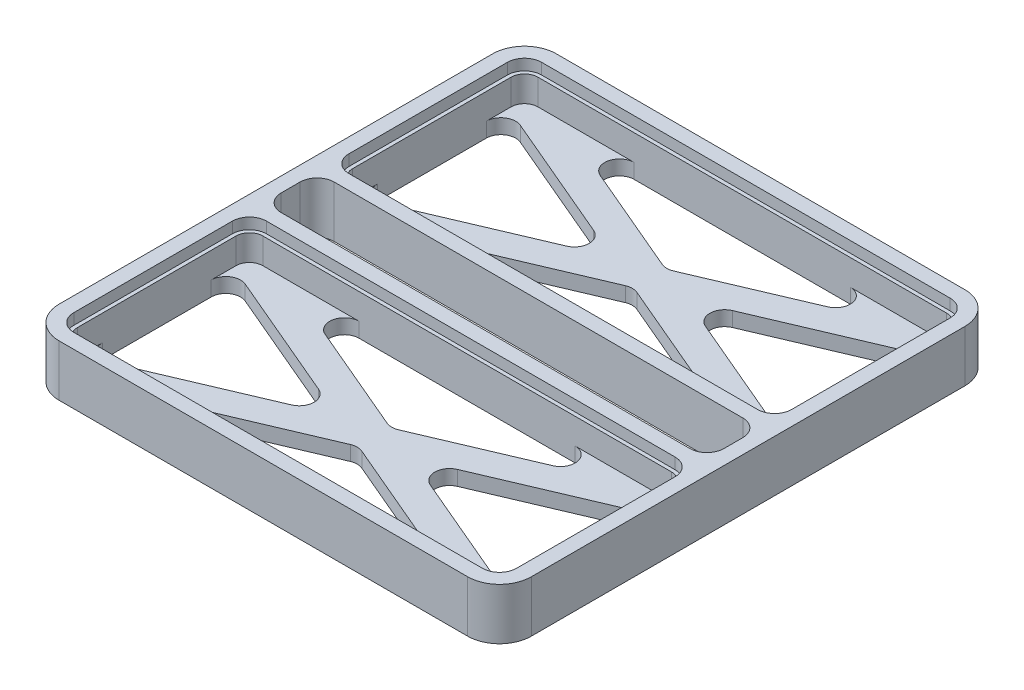
SolidWorks part; units mm, degrees
ref_plane "Спереди" through (0, 0, 0) normal (0, 0, 1) x (1, 0, 0)
ref_plane "Сверху" through (0, 0, 0) normal (0, 1, 0) x (1, 0, 0)
ref_plane "Справа" through (0, 0, 0) normal (1, 0, 0) x (0, 0, -1)
sketch "Эскиз1" plane through (0, 0, 0) normal (0, 1, 0) x (1, 0, 0)
  line L5 (14.6888, -12.6) -> (-14.6888, -12.6)
  line L6 (29.6, -7.4013) -> (29.6, 7.4013)
  line L7 (-32.1, -15.1) -> (32.1, -15.1)
  line L8 (-32.1, -15.1) -> (-32.1, 10.775)
  line L9 (-27.775, 15.1) -> (27.775, 15.1)
  line L10 (32.1, -15.1) -> (32.1, 10.775)
  line L11 (14.6888, 12.6) -> (-14.6888, 12.6)
  line L12 (-29.6, -7.4013) -> (-29.6, 7.4013)
  line L13 (-27.775, -52.5) -> (27.775, -52.5)
  line L14 (-0.7833, 2.5071) -> (-15.4722, 8.7598)
  line L15 (0.7833, 2.5071) -> (15.4722, 8.7598)
  line L16 (-9.4294, -1.8402) -> (-26.8167, -9.2415)
  line L17 (9.4294, -1.8402) -> (26.8167, -9.2415)
  line L18 (-0.7833, -2.5071) -> (-15.4722, -8.7598)
  line L19 (9.4294, 1.8402) -> (26.8167, 9.2415)
  line L20 (-0.7833, -34.8929) -> (-15.4722, -28.6402)
  line L21 (0.7833, -2.5071) -> (15.4722, -8.7598)
  line L22 (-9.4294, 1.8402) -> (-26.8167, 9.2415)
  line L23 (32.1, -48.175) -> (32.1, -22.3)
  line L24 (-9.4294, -39.2402) -> (-26.8167, -46.6415)
  line L25 (14.6888, -24.8) -> (-14.6888, -24.8)
  line L26 (0.7833, -39.9071) -> (15.4722, -46.1598)
  line L27 (-9.4294, -35.5598) -> (-26.8167, -28.1585)
  line L28 (29.6, -44.8013) -> (29.6, -29.9987)
  line L30 (9.4294, -39.2402) -> (26.8167, -46.6415)
  line L32 (-29.6, -44.8013) -> (-29.6, -29.9987)
  line L33 (-32.1, -22.3) -> (32.1, -22.3)
  line L34 (14.6888, -50) -> (-14.6888, -50)
  line L36 (-0.7833, -39.9071) -> (-15.4722, -46.1598)
  line L37 (-32.1, -48.175) -> (-32.1, -22.3)
  line L38 (0.7833, -34.8929) -> (15.4722, -28.6402)
  line L40 (9.4294, -35.5598) -> (26.8167, -28.1585)
  arc A0 (-26.8167, 9.2415) -> (-29.6, 7.4013) centre (-27.6, 7.4013) ccw
  arc A1 (-9.4294, -1.8402) -> (-9.4294, 1.8402) centre (-10.2128, 0) ccw
  arc A2 (-29.6, -7.4013) -> (-26.8167, -9.2415) centre (-27.6, -7.4013) ccw
  arc A3 (-15.4722, -8.7598) -> (-14.6888, -12.6) centre (-14.6888, -10.6) ccw
  arc A4 (0.7833, -2.5071) -> (-0.7833, -2.5071) centre (0, -4.3473) ccw
  arc A5 (14.6888, -12.6) -> (15.4722, -8.7598) centre (14.6888, -10.6) ccw
  arc A6 (9.4294, 1.8402) -> (9.4294, -1.8402) centre (10.2128, 0) ccw
  arc A7 (29.6, 7.4013) -> (26.8167, 9.2415) centre (27.6, 7.4013) ccw
  arc A8 (26.8167, -9.2415) -> (29.6, -7.4013) centre (27.6, -7.4013) ccw
  arc A9 (-0.7833, 2.5071) -> (0.7833, 2.5071) centre (0, 4.3473) ccw
  arc A10 (15.4722, 8.7598) -> (14.6888, 12.6) centre (14.6888, 10.6) ccw
  arc A11 (-14.6888, 12.6) -> (-15.4722, 8.7598) centre (-14.6888, 10.6) ccw
  arc A12 (15.4722, -28.6402) -> (14.6888, -24.8) centre (14.6888, -26.8) ccw
  arc A13 (-14.6888, -24.8) -> (-15.4722, -28.6402) centre (-14.6888, -26.8) ccw
  arc A14 (-15.4722, -46.1598) -> (-14.6888, -50) centre (-14.6888, -48) ccw
  arc A15 (0.7833, -39.9071) -> (-0.7833, -39.9071) centre (0, -41.7473) ccw
  arc A16 (-0.7833, -34.8929) -> (0.7833, -34.8929) centre (0, -33.0527) ccw
  arc A17 (9.4294, -35.5598) -> (9.4294, -39.2402) centre (10.2128, -37.4) ccw
  arc A18 (-26.8167, -28.1585) -> (-29.6, -29.9987) centre (-27.6, -29.9987) ccw
  arc A19 (26.8167, -46.6415) -> (29.6, -44.8013) centre (27.6, -44.8013) ccw
  arc A20 (-9.4294, -39.2402) -> (-9.4294, -35.5598) centre (-10.2128, -37.4) ccw
  arc A21 (-29.6, -44.8013) -> (-26.8167, -46.6415) centre (-27.6, -44.8013) ccw
  arc A22 (29.6, -29.9987) -> (26.8167, -28.1585) centre (27.6, -29.9987) ccw
  arc A23 (14.6888, -50) -> (15.4722, -46.1598) centre (14.6888, -48) ccw
  arc A29 (27.775, 15.1) -> (32.1, 10.775) centre (27.775, 10.775) cw
  arc A30 (-27.775, 15.1) -> (-32.1, 10.775) centre (-27.775, 10.775) ccw
  arc A31 (27.775, -52.5) -> (32.1, -48.175) centre (27.775, -48.175) ccw
  arc A32 (-27.775, -52.5) -> (-32.1, -48.175) centre (-27.775, -48.175) cw
  point P0 (0, 0)
  point P10 (0, 0)
  point P11 (-32.1, -15.1)
  point P17 (0, -37.4)
  point P30 (0, -37.4)
  point P47 (32.1, -22.3)
sketch "Эскиз2" plane through (0, 0, 0) normal (0, 1, 0) x (1, 0, 0)
  line L1 (-30.1, -13.1) -> (30.1, -13.1)
  line L2 (-30.1, -13.1) -> (-30.1, 13.1)
  line L3 (-30.1, 13.1) -> (30.1, 13.1)
  line L4 (30.1, -13.1) -> (30.1, 13.1)
  line L5 (27.775, -12.6) -> (-27.775, -12.6)
  line L6 (29.6, -10.775) -> (29.6, 10.775)
  line L11 (27.775, 12.6) -> (-27.775, 12.6)
  line L12 (-29.6, -10.775) -> (-29.6, 10.775)
  line L20 (-30.1, -50.5) -> (-30.1, -24.3)
  line L25 (30.1, -50.5) -> (30.1, -24.3)
  line L26 (27.775, -24.8) -> (-27.775, -24.8)
  line L29 (29.6, -48.175) -> (29.6, -26.625)
  line L31 (-30.1, -50.5) -> (30.1, -50.5)
  line L32 (27.775, -50) -> (-27.775, -50)
  line L33 (-30.1, -24.3) -> (30.1, -24.3)
  line L36 (-29.6, -48.175) -> (-29.6, -26.625)
  arc A0 (-27.775, -50) -> (-29.6, -48.175) centre (-27.775, -48.175) cw
  arc A1 (27.775, -50) -> (29.6, -48.175) centre (27.775, -48.175) ccw
  arc A2 (29.6, -26.625) -> (27.775, -24.8) centre (27.775, -26.625) ccw
  arc A3 (-29.6, -26.625) -> (-27.775, -24.8) centre (-27.775, -26.625) cw
  arc A4 (-27.775, -12.6) -> (-29.6, -10.775) centre (-27.775, -10.775) cw
  arc A5 (27.775, -12.6) -> (29.6, -10.775) centre (27.775, -10.775) ccw
  arc A6 (29.6, 10.775) -> (27.775, 12.6) centre (27.775, 10.775) ccw
  arc A7 (-29.6, 10.775) -> (-27.775, 12.6) centre (-27.775, 10.775) cw
  point P0 (0, 0)
  point P5 (0, -37.4)
  point P10 (0, 0)
  point P29 (0, -37.4)
  dimension "D1" = 1.825
sketch "Эскиз3" plane through (0, 0, 0) normal (0, 1, 0) x (1, 0, 0)
  line L0 (-30.1, -17.425) -> (-30.1, -19.975)
  line L1 (-27.775, -13.1) -> (27.775, -13.1)
  line L2 (-30.1, -10.775) -> (-30.1, 10.775)
  line L3 (-27.775, 13.1) -> (27.775, 13.1)
  line L4 (30.1, -10.775) -> (30.1, 10.775)
  line L7 (-27.775, -15.1) -> (27.775, -15.1)
  line L8 (-32.1, -15.1) -> (-32.1, 10.775)
  line L9 (-27.775, 15.1) -> (27.775, 15.1)
  line L10 (32.1, -15.1) -> (32.1, 10.775)
  line L13 (-32.1, -15.1) -> (-32.1, -22.3)
  line L14 (30.1, -17.425) -> (30.1, -19.975)
  line L15 (32.1, -15.1) -> (32.1, -22.3)
  line L28 (-27.775, -52.5) -> (27.775, -52.5)
  line L29 (32.1, -48.175) -> (32.1, -22.3)
  line L31 (-30.1, -48.175) -> (-30.1, -26.625)
  line L32 (-27.775, -22.3) -> (27.775, -22.3)
  line L33 (30.1, -48.175) -> (30.1, -26.625)
  line L35 (-32.1, -48.175) -> (-32.1, -22.3)
  line L38 (-27.775, -24.3) -> (27.775, -24.3)
  line L40 (-27.775, -50.5) -> (27.775, -50.5)
  arc A12 (-27.775, 13.1) -> (-30.1, 10.775) centre (-27.775, 10.775) ccw
  arc A14 (-27.775, 15.1) -> (-32.1, 10.775) centre (-27.775, 10.775) ccw
  arc A15 (-30.1, -10.775) -> (-27.775, -13.1) centre (-27.775, -10.775) ccw
  arc A16 (30.1, 10.775) -> (27.775, 13.1) centre (27.775, 10.775) ccw
  arc A17 (27.775, -13.1) -> (30.1, -10.775) centre (27.775, -10.775) ccw
  arc A18 (-30.1, -48.175) -> (-27.775, -50.5) centre (-27.775, -48.175) ccw
  arc A19 (-27.775, -24.3) -> (-30.1, -26.625) centre (-27.775, -26.625) ccw
  arc A20 (30.1, -26.625) -> (27.775, -24.3) centre (27.775, -26.625) ccw
  arc A21 (27.775, -50.5) -> (30.1, -48.175) centre (27.775, -48.175) ccw
  arc A22 (32.1, 10.775) -> (27.775, 15.1) centre (27.775, 10.775) ccw
  arc A23 (-32.1, -48.175) -> (-27.775, -52.5) centre (-27.775, -48.175) ccw
  arc A24 (27.775, -52.5) -> (32.1, -48.175) centre (27.775, -48.175) ccw
  arc A25 (-30.1, -19.975) -> (-27.775, -22.3) centre (-27.775, -19.975) ccw
  arc A26 (-27.775, -15.1) -> (-30.1, -17.425) centre (-27.775, -17.425) ccw
  arc A27 (30.1, -17.425) -> (27.775, -15.1) centre (27.775, -17.425) ccw
  arc A28 (27.775, -22.3) -> (30.1, -19.975) centre (27.775, -19.975) ccw
  point P10 (0, 0)
  point P11 (-32.1, -15.1)
  point P31 (32.1, -22.3)
extrude "Бобышка-Вытянуть1" add sketch "Эскиз1" along normal blind 2
extrude "Бобышка-Вытянуть2" add sketch "Эскиз3" along normal blind 7 contours L7 L10 L9 L8 L4 L1 L2 L3 | L35 L28 L29 L32 L40 L31 L38 L33 region at (-31.1677, 0, 2.1625)
extrude "Бобышка-Вытянуть3" add sketch "Эскиз2" along normal blind 5.5 contours L1 L4 L3 L2 L5 L12 L11 L6 | L33 L20 L31 L25 L32 L36 L26 L29 region at (-30.0343, 0, 0) region at (-30.0343, 0, 37.4)
sketch "Эскиз4" plane through (0, 0, 0) normal (0, -1, 0) x (1, 0, 0)
  line L0 (-29.6, 47.6) -> (-32.1, 37) construction
  line L1 (30.5, 6.5) -> (32.1, -4.1) construction
  circle A0 centre (-30.85, 42.3) radius 0.5
  circle A1 centre (3.95, 37.4) radius 0.5
  circle A2 centre (31.3, 36.2) radius 0.5
  circle A3 centre (31.3, 1.2) radius 0.5
  circle A4 centre (3.95, 0) radius 0.5
  circle A5 centre (-30.85, -4.9) radius 0.5
extrude "Вырез-Вытянуть1" cut sketch "Эскиз4" against normal blind 0.5
